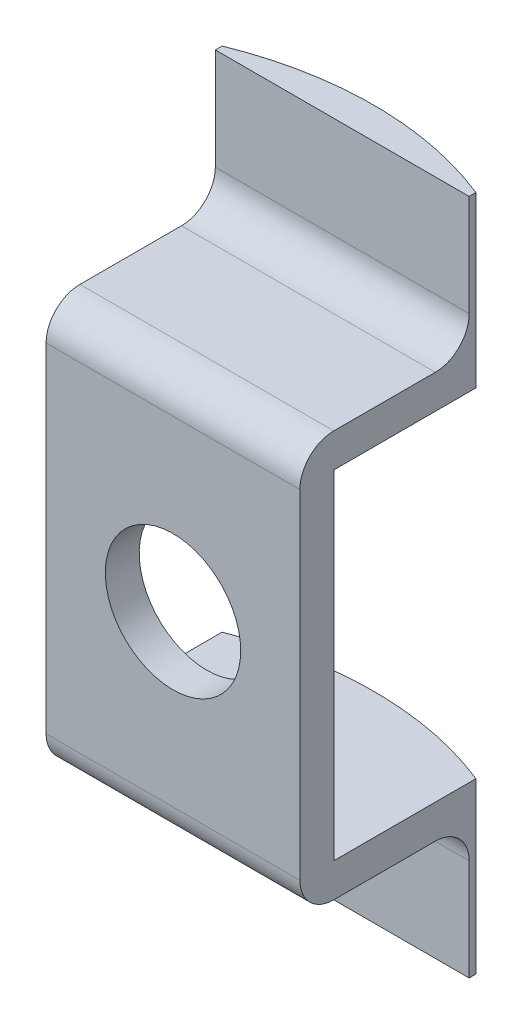
SolidWorks part; units mm, degrees
ref_plane "Front Plane" through (0, 0, 0) normal (1, 0, 0) x (0, 1, 0)
ref_plane "Top Plane" through (0, 0, 0) normal (0, 0, 1) x (0, 1, 0)
ref_plane "Right Plane" through (0, 0, 0) normal (0, 1, 0) x (-1, 0, 0)
sketch "Sketch1" plane through (0, 0, 0) normal (1, 0, 0) x (0, 1, 0)
  line L0 (-20, 0) -> (-10, 0)
  line L1 (-10, 0) -> (-10, 10)
  line L2 (-10, 10) -> (10, 10)
  line L3 (10, 10) -> (10, 0)
  line L4 (10, 0) -> (20, 0)
  line L5 (-3.7567, 0) -> (6.4974, 0) construction
  line L6 (0, 5.9632) -> (0, -4.4167) construction
  line L7 (-20, 0) -> (-20, 2)
  line L8 (-20, 2) -> (-12, 2)
  line L9 (-12, 2) -> (-12, 12)
  line L10 (-12, 12) -> (12, 12)
  line L11 (12, 12) -> (12, 2)
  line L12 (12, 2) -> (20, 2)
  line L13 (20, 0) -> (20, 2)
  dimension "D1" = 2
  dimension "D2" = 2
  dimension "D3" = 2
  dimension "D4" = 2
  dimension "D5" = 2
  dimension "D6" = 12
  dimension "D7" = 20
  dimension "D8" = 10
extrude "Boss-Extrude1" add sketch "Sketch1" along normal blind 15
sketch "Sketch2" plane through (0, 0, 12) normal (0, 0, 1) x (1, 0, 0)
  line L0 (7.5, 36) -> (7.5, -12) construction
  line L1 (0, 0) -> (15, 0) construction
  line L2 (15, -12) -> (0, -12) construction
  line L3 (15, 12) -> (15, -12) construction
  circle A0 centre (7.5, 0) radius 4
  point P3 (7.5, 12)
  dimension "D1" = 8
extrude "Cut-Extrude1" cut sketch "Sketch2" against normal blind 15
sketch "Sketch3" plane through (0, 20, 0) normal (0, 1, 0) x (-1, 0, 0)
  line L0 (-15, 1.6) -> (-15, -1.0407)
  line L1 (-15, -1.0407) -> (0, -1.0913)
  line L2 (0, -1.0913) -> (0, 1.6)
  line L3 (0, 0) -> (0, 2) construction
  line L4 (-15, 2) -> (0, 2) construction
  line L5 (-15, 0) -> (-15, 2) construction
  arc A0 (-15, 1.6) -> (0, 1.6) centre (-7.5, 20.1405) ccw
  point P3 (0, 0)
  point P4 (-15, 1.6)
  point P8 (0, 0)
  point P9 (0, 1.5632)
  point P14 (0, 0)
  point P16 (-15, 1.4791)
  point P17 (-15, 2)
  dimension "D1" = 20
  dimension "D2" = 0.4
  dimension "D3" = 0.4
extrude "Cut-Extrude2" cut sketch "Sketch3" against normal through all
fillet "Fillet1" radius 2 2 edges at (7.5, -12, 2) (7.5, 12, 2)
fillet "Fillet2" radius 2 2 edges at (7.5, 12, 12) (7.5, -12, 12)
